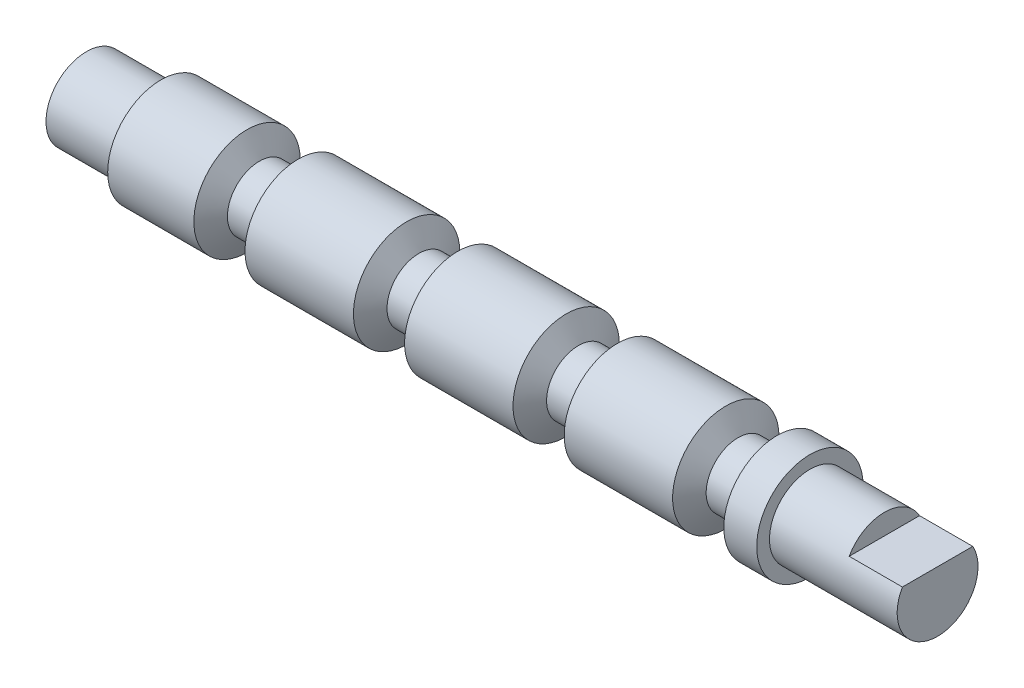
SolidWorks part; units mm, degrees
ref_plane "Front Plane" through (0, 0, 0) normal (0, 0, 1) x (1, 0, 0)
ref_plane "Top Plane" through (0, 0, 0) normal (0, 1, 0) x (1, 0, 0)
ref_plane "Right Plane" through (0, 0, 0) normal (1, 0, 0) x (0, 0, -1)
sketch "Sketch2" plane through (0, 0, 0) normal (0, 1, 0) x (1, 0, 0)
  line L1 (40, -5) -> (-40, -5)
  line L5 (-30.0491, 0) -> (-24.9047, 0)
  line L6 (-5.0953, 0) -> (-6.25, -2)
  line L7 (-6.25, -2) -> (-8.75, -2)
  line L8 (-8.75, -2) -> (-9.9047, 0)
  line L9 (-20.0953, 0) -> (-21.25, -2)
  line L10 (-21.25, -2) -> (-23.75, -2)
  line L11 (-23.75, -2) -> (-24.9047, 0)
  line L21 (-5.0953, 0) -> (5.0953, 0)
  line L22 (-20.0953, 0) -> (-9.9047, 0)
  line L25 (-30.0491, 0) -> (-40, 0)
  line L30 (-40, 0) -> (-40, -5)
  line L31 (0, 0) -> (0, -5) construction
  line L32 (40, 0) -> (40, -5)
  line L33 (30.0491, 0) -> (40, 0)
  line L34 (20.0953, 0) -> (9.9047, 0)
  line L35 (23.75, -2) -> (24.9047, 0)
  line L36 (21.25, -2) -> (23.75, -2)
  line L37 (20.0953, 0) -> (21.25, -2)
  line L38 (8.75, -2) -> (9.9047, 0)
  line L39 (6.25, -2) -> (8.75, -2)
  line L40 (5.0953, 0) -> (6.25, -2)
  line L41 (30.0491, 0) -> (24.9047, 0)
  point P2 (-7.5, -2)
  point P6 (-22.5, -2)
  dimension "D2" = 5
  dimension "D3" = 3
  dimension "D4" = 120
  dimension "D5" = 120
  dimension "D6" = 7.5
  dimension "D7" = 2.5
  dimension "D8" = 22.5
  dimension "D9" = 120
  dimension "D10" = 120
  dimension "D11" = 2.5
  dimension "D12" = 40
revolve "Revolve1" add sketch "Sketch2" angle 360 about L1
sketch "Sketch3" plane through (40, 0, 0) normal (1, 0, 0) x (0, 0, -1)
  circle A0 centre (-5, 0) radius 3.8
  circle A2 centre (-5, 0) radius 5
  circle A3 centre (-5, 0) radius 5
  dimension "D2" = 0
  dimension "D1" = 7.6
sketch "Sketch4" plane through (-40, 0, 0) normal (-1, 0, 0) x (0, 0, 1)
  circle A0 centre (5, 0) radius 3.8
  circle A2 centre (5, 0) radius 5
  circle A3 centre (5, 0) radius 5
  dimension "D1" = 7.6
  dimension "D2" = 0
extrude "Cut-Extrude2" cut sketch "Sketch4" against normal blind 7
extrude "Cut-Extrude4" cut sketch "Sketch3" against normal blind 12
sketch "Sketch5" plane through (40, 0, 0) normal (1, 0, 0) x (0, 0, -1)
  line L0 (-8.3076, 1.8709) -> (-1.6924, 1.8709)
  line L1 (0, 0) -> (-5, 0) construction
  circle A1 centre (-5, 0) radius 3.8
  arc A2 (-1.6924, 1.8709) -> (-8.3076, 1.8709) centre (-5, 0) ccw
  dimension "D2" = 1.8709
  dimension "D1" = 0
extrude "Cut-Extrude5" cut sketch "Sketch5" against normal blind 5
